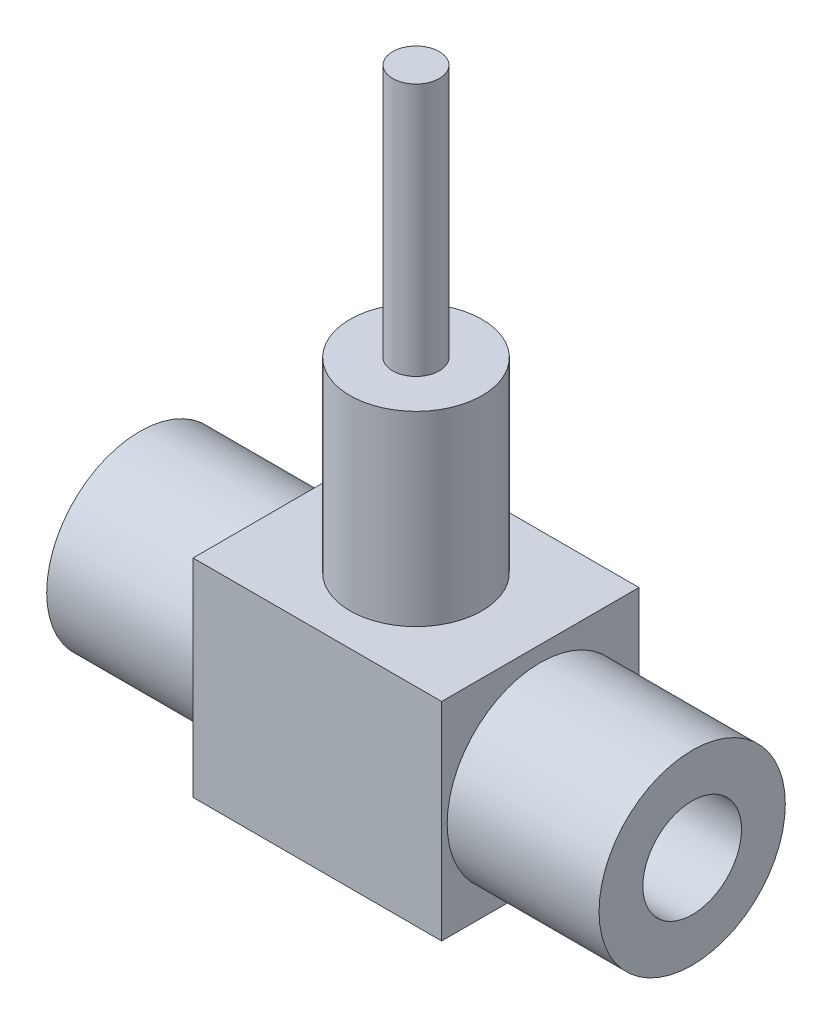
SolidWorks part; units mm, degrees
ref_plane "Front Plane" through (0, 0, 0) normal (0, 0, 1) x (1, 0, 0)
ref_plane "Top Plane" through (0, 0, 0) normal (0, 1, 0) x (1, 0, 0)
ref_plane "Right Plane" through (0, 0, 0) normal (1, 0, 0) x (0, 0, -1)
sketch "Body Sketch" plane through (0, 0, 0) normal (0, 0, 1) x (1, 0, 0)
  line L0 (-16, -12.7) -> (16, -12.7)
  line L1 (16, -12.7) -> (16, 14)
  line L2 (16, 14) -> (-16, 14)
  line L3 (-16, 14) -> (-16, -12.7)
extrude "Body" add sketch "Body Sketch" along normal mid plane 25.4
ref_axis "Engine Axis" through (39.105, 0, 0) along (-1, 0, 0)
ref_axis "Stem Axis" through (0, -16.865, 0) along (0, 1, 0)
sketch "Nut +X Sketch" plane through (0, 0, 0) normal (0, 0, 1) x (1, 0, 0)
  line L0 (-1000, 0) -> (1000, 0) construction
  line L1 (16, 0) -> (35.55, 0)
  line L2 (35.55, 0) -> (35.55, 11.988)
  line L3 (35.55, 11.988) -> (16, 11.988)
  line L4 (16, 11.988) -> (16, 0)
revolve "Nut +X" add sketch "Nut +X Sketch" angle 360 about L0
sketch "Nut -X Sketch" plane through (0, 0, 0) normal (0, 0, 1) x (1, 0, 0)
  line L0 (-1000, 0) -> (1000, 0) construction
  line L1 (-35.55, 0) -> (-16, 0)
  line L2 (-16, 0) -> (-16, 11.988)
  line L3 (-16, 11.988) -> (-35.55, 11.988)
  line L4 (-35.55, 11.988) -> (-35.55, 0)
revolve "Nut -X" add sketch "Nut -X Sketch" angle 360 about L0
sketch "Socket +X Sketch" plane through (0, 0, 0) normal (0, 0, 1) x (1, 0, 0)
  line L0 (-1000, 0) -> (1000, 0) construction
  line L1 (12.65, 0) -> (36.55, 0)
  line L2 (36.55, 0) -> (36.55, 6.35)
  line L3 (36.55, 6.35) -> (12.65, 6.35)
  line L4 (12.65, 6.35) -> (12.65, 0)
revolve "Socket +X" cut sketch "Socket +X Sketch" angle 360 about L0
sketch "Socket -X Sketch" plane through (0, 0, 0) normal (0, 0, 1) x (1, 0, 0)
  line L0 (-1000, 0) -> (1000, 0) construction
  line L1 (-36.55, 0) -> (-12.65, 0)
  line L2 (-12.65, 0) -> (-12.65, 6.35)
  line L3 (-12.65, 6.35) -> (-36.55, 6.35)
  line L4 (-36.55, 6.35) -> (-36.55, 0)
revolve "Socket -X" cut sketch "Socket -X Sketch" angle 360 about L0
sketch "Stem Sketch" plane through (0, 0, 0) normal (0, 0, 1) x (1, 0, 0)
  line L0 (0, -500) -> (0, 500) construction
  line L1 (0, 14) -> (8.5, 14)
  line L2 (8.5, 14) -> (8.5, 38)
  line L3 (8.5, 38) -> (3, 38)
  line L4 (3, 38) -> (3, 70.6)
  line L5 (3, 70.6) -> (0, 70.6)
  line L6 (0, 70.6) -> (0, 14)
revolve "Stem" add sketch "Stem Sketch" angle 360 about L0
ref_plane "Torch Port Face" through (0, 0, -12.7) normal (0, 0, 1) x (1, 0, 0)
sketch "Torch Nitrous Port Sketch" plane through (0, 0, -12.7) normal (0, 0, 1) x (1, 0, 0)
  circle A0 centre (-8, 0) radius 3.5
extrude "Torch Nitrous Port" cut sketch "Torch Nitrous Port Sketch" along normal blind 8.6
sketch "Torch Nitrous Drilling Sketch" plane through (0, 0, -12.7) normal (0, 0, 1) x (1, 0, 0)
  circle A0 centre (-8, 0) radius 1
extrude "Torch Nitrous Drilling" cut sketch "Torch Nitrous Drilling Sketch" along normal blind 12.7
